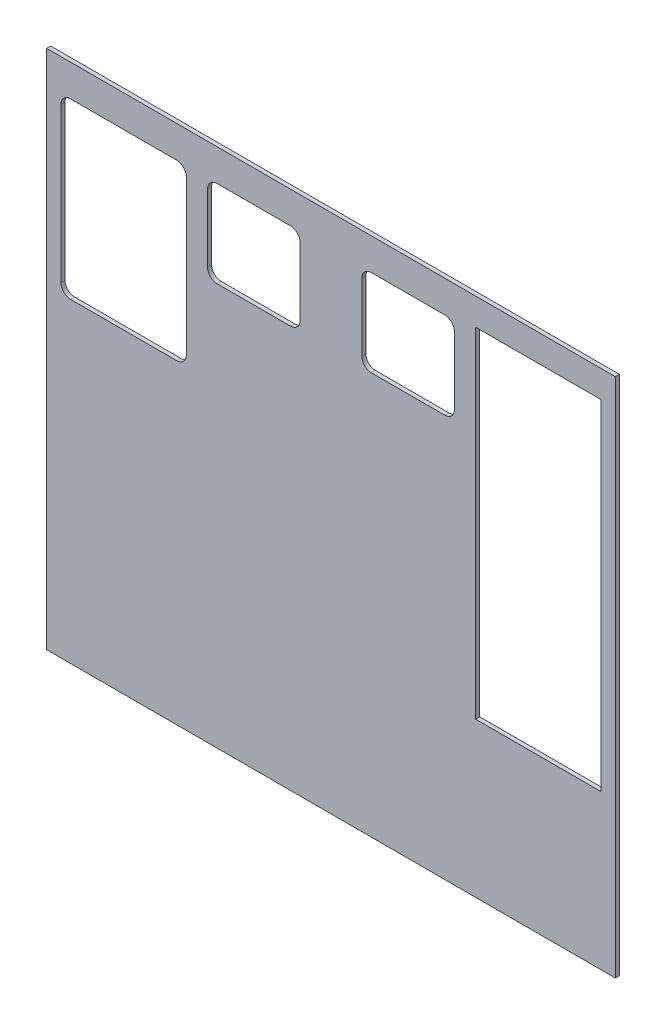
SolidWorks part; units mm, degrees
material "ASTM A36 Steel"
ref_plane "Front Plane" through (0, 0, 0) normal (0, 0, 1) x (1, 0, 0)
ref_plane "Top Plane" through (0, 0, 0) normal (0, 1, 0) x (1, 0, 0)
ref_plane "Right Plane" through (0, 0, 0) normal (1, 0, 0) x (0, 0, -1)
sketch "Sketch1" plane through (0, 0, 0) normal (0, 0, 1) x (1, 0, 0)
  line L0 (-193.04, 0) -> (-193.04, 349.25)
  line L1 (0, 0) -> (0, 358.775) construction
  line L2 (193.04, 0) -> (-193.04, 0)
  line L3 (193.04, 0) -> (193.04, 349.25)
  line L4 (74.93, 264.795) -> (26.67, 264.795)
  line L5 (-171.45, 321.945) -> (-101.6, 321.945)
  line L6 (-177.8, 315.595) -> (-177.8, 213.995)
  line L7 (-171.45, 207.645) -> (-101.6, 207.645)
  line L8 (-95.25, 315.595) -> (-95.25, 213.995)
  line L9 (-74.93, 321.945) -> (-26.67, 321.945)
  line L10 (-81.28, 315.595) -> (-81.28, 271.145)
  line L11 (-74.93, 264.795) -> (-26.67, 264.795)
  line L12 (-20.32, 315.595) -> (-20.32, 271.145)
  line L17 (95.25, 325.12) -> (177.8, 325.12)
  line L18 (95.25, 325.12) -> (95.25, 101.6)
  line L19 (95.25, 101.6) -> (177.8, 101.6)
  line L20 (177.8, 325.12) -> (177.8, 101.6)
  line L21 (20.32, 315.595) -> (20.32, 271.145)
  line L22 (74.93, 321.945) -> (26.67, 321.945)
  line L23 (81.28, 315.595) -> (81.28, 271.145)
  arc A0 (193.04, 349.25) -> (-193.04, 349.25) centre (0, -1602.1262) ccw
  arc A1 (-101.6, 207.645) -> (-95.25, 213.995) centre (-101.6, 213.995) ccw
  arc A2 (-95.25, 315.595) -> (-101.6, 321.945) centre (-101.6, 315.595) ccw
  arc A3 (-177.8, 213.995) -> (-171.45, 207.645) centre (-171.45, 213.995) ccw
  arc A4 (-171.45, 321.945) -> (-177.8, 315.595) centre (-171.45, 315.595) ccw
  arc A5 (-20.32, 315.595) -> (-26.67, 321.945) centre (-26.67, 315.595) ccw
  arc A6 (-26.67, 264.795) -> (-20.32, 271.145) centre (-26.67, 271.145) ccw
  arc A7 (-81.28, 271.145) -> (-74.93, 264.795) centre (-74.93, 271.145) ccw
  arc A8 (-74.93, 321.945) -> (-81.28, 315.595) centre (-74.93, 315.595) ccw
  arc A9 (81.28, 271.145) -> (74.93, 264.795) centre (74.93, 271.145) cw
  arc A10 (26.67, 264.795) -> (20.32, 271.145) centre (26.67, 271.145) cw
  arc A11 (20.32, 315.595) -> (26.67, 321.945) centre (26.67, 315.595) cw
  arc A12 (74.93, 321.945) -> (81.28, 315.595) centre (74.93, 315.595) cw
  point P28 (-95.25, 321.945)
  point P31 (-177.8, 207.645)
  point P34 (-177.8, 321.945)
  point P37 (-20.32, 321.945)
  point P42 (-81.28, 264.795)
  point P45 (-81.28, 321.945)
  point P60 (193.04, 349.25)
  point P64 (-193.04, 349.25)
  dimension "D1" = 358.775
  dimension "D12" = 20.32
  dimension "D16" = 101.6
  dimension "D8" = 6.35
  dimension "D11" = 6.35
  dimension "D2" = 349.25
  dimension "D3" = 386.08
  dimension "D4" = 82.55
  dimension "D5" = 114.3
  dimension "D6" = 207.645
  dimension "D7" = 95.25
  dimension "D9" = 57.15
  dimension "D10" = 60.96
  dimension "D13" = 15.24
  dimension "D14" = 13.97
  dimension "D15" = 223.52
extrude "Boss-Extrude1" add sketch "Sketch1" along normal blind 2.667 contours L2 A8 A5 L8 A1 | L1 L2 L3 A0 L17 L20 L19 L18 L22 A12 L23 A9 L4 A10 L21 A11 region at (-92.0762, 156.0138, 0) region at (83.47, 155.2545, 0)
sketch "Sketch2" plane through (0, 0, 2.667) normal (0, 0, 1) x (1, 0, 0)
  line L0 (-193.04, 0) -> (-193.04, 349.25) construction
  line L1 (193.04, 0) -> (193.04, 349.25) construction
  line L2 (-187.198, 342.9) -> (187.198, 342.9)
  line L4 (-187.198, 0) -> (-187.198, 342.9)
  line L5 (187.198, 0) -> (187.198, 342.9)
  line L6 (-20.32, 315.595) -> (-20.32, 271.145) construction
  line L7 (193.04, 0) -> (-193.04, 0) construction
  line L8 (0, 0) -> (0, 358.775) construction
  arc A0 (193.04, 349.25) -> (-193.04, 349.25) centre (0, -1602.1262) ccw construction
  line M17 (-193.04, 0) -> (193.04, 0)
  line M18 (193.04, 0) -> (193.04, 349.25)
  arc M19 (193.04, 349.25) -> (-193.04, 349.25) centre (0, -1602.1262) ccw
  line M20 (-193.04, 349.25) -> (-193.04, 0)
  dimension "D1" = 342.9
  dimension "D2" = 374.396
extrude "CornerRadiusAllowance" cut sketch "Sketch2" against normal through all contours L2 L8 L4 M19 M20 M17 | L8 L2 L5 M17 M18 M19 region at (-191.2721, 171.45, 2.667) region at (4.0741, 350.8375, 2.667)
